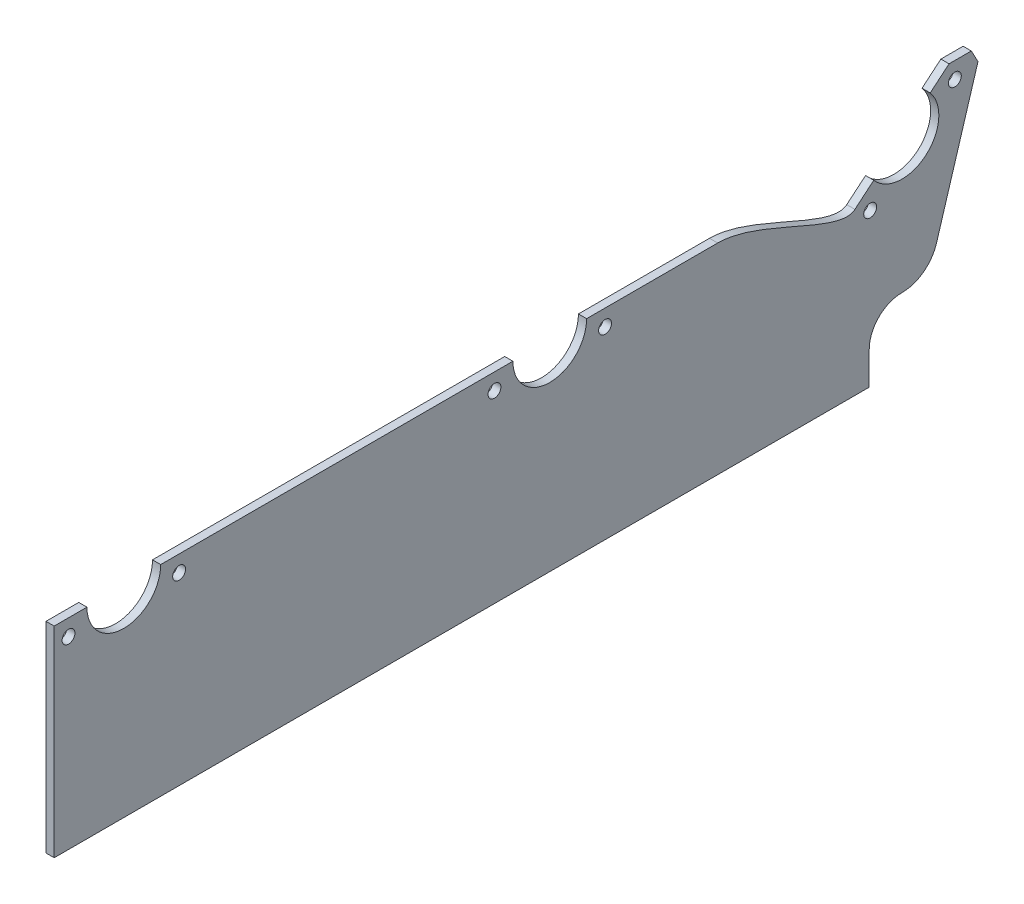
SolidWorks part; units mm, degrees
material "6061 Alloy"
ref_plane "Front Plane" through (0, 0, 0) normal (0, 0, 1) x (1, 0, 0)
ref_plane "Top Plane" through (0, 0, 0) normal (0, 1, 0) x (1, 0, 0)
ref_plane "Right Plane" through (0, 0, 0) normal (1, 0, 0) x (0, 0, -1)
sketch "Sketch1" plane through (0, 0, 0) normal (1, 0, 0) x (0, 0, -1)
  line L0 (-12.7, -12.7) -> (-328.6125, -12.7)
  line L1 (-328.6125, -12.7) -> (-328.6125, 65.0875)
  line L2 (-328.6125, 65.0875) -> (-315.9125, 65.0875)
  line L3 (-287.3375, 65.0875) -> (-150.8125, 65.0875)
  line L5 (10.9449, 74.2713) -> (18.2432, 80.3953)
  line L7 (-328.6125, 12.7) -> (13.3654, 12.7) construction
  line L8 (-12.7, -12.7) -> (-12.7, 0)
  line L9 (0, 12.4079) -> (0, 12.7) construction
  line L10 (13.3654, 22.6047) -> (30.9432, 80.3953)
  line L12 (-10.9449, 55.9037) -> (10.9449, 74.2713) construction
  line L13 (18.2432, 80.3953) -> (30.9432, 80.3953)
  line L14 (-122.2375, 65.0875) -> (-71.4375, 65.0875)
  line L15 (-10.9449, 55.9037) -> (-18.2432, 49.7797)
  line L18 (0, 65.0875) -> (-136.525, 65.0875) construction
  arc A3 (0, 12.7) -> (13.3654, 22.6047) centre (0, 26.67) ccw
  arc A4 (0, 12.7) -> (-12.7, 0) centre (0, 0) ccw
  circle A5 centre (0, 0) radius 12.4079 construction
  arc A6 (-315.9125, 65.0875) -> (-287.3375, 65.0875) centre (-301.625, 65.0875) ccw
  arc A7 (-150.8125, 65.0875) -> (-122.2375, 65.0875) centre (-136.525, 65.0875) ccw
  arc A8 (-10.9449, 55.9037) -> (10.9449, 74.2713) centre (0, 65.0875) ccw
  spline S0 degree 3 poles (-18.2432, 49.7797) (-24.729, 44.3374) (-54.5042, 65.0875) (-71.4375, 65.0875) knots 0 0 0 0 1 1 1 1
  point P4 (-170.6562, -12.7)
  dimension "D1" = 25.4
  dimension "D3" = 12.7
  dimension "D5" = 28.575
  dimension "D6" = 38.1
  dimension "D7" = 13.97
  dimension "D8" = 12.7
  dimension "D10" = 24.8158
  dimension "D13" = 9.5273
  dimension "D14" = 140
  dimension "D15" = 50.8
  dimension "D16" = 50.8
  dimension "D17" = 25.4
  dimension "D2" = 0
  dimension "D4" = 12.7
  dimension "D9" = 12.7
  dimension "D11" = 301.625
  dimension "D12" = 301.625
extrude "Boss-Extrude1" add sketch "Sketch1" along normal blind 3.175
hole_wizard "#10 Clearance Hole1" positions "Sketch2" profile "Sketch3" hole size "#10" standard "ANSI Inch" end condition through all
sketch "Sketch2" plane through (3.175, 0, 0) normal (1, 0, 0) x (0, 0, -1)
  line L0 (-323.0562, 58.7375) -> (-280.1937, 58.7375) construction
  line L2 (-157.9562, 58.7375) -> (-115.0937, 58.7375) construction
  line L4 (-12.3356, 46.4474) -> (20.499, 73.9989) construction
  line L6 (-315.9125, 65.0875) -> (-328.6125, 65.0875) construction
  line L7 (-301.625, 58.7375) -> (-301.625, 65.0875) construction
  line L9 (-136.525, 65.0875) -> (-136.525, 58.7375) construction
  line L11 (0, 65.0875) -> (4.0817, 60.2231) construction
  line L14 (18.2432, 80.3953) -> (10.9449, 74.2713) construction
  line L15 (18.2432, 80.3953) -> (10.9449, 74.2713) construction
  point P0 (-323.0562, 58.7375)
  point P2 (-280.1938, 58.7375)
  point P4 (-157.9562, 58.7375)
  point P6 (-115.0937, 58.7375)
  point P8 (-12.3356, 46.4474)
  point P10 (20.499, 73.9989)
  dimension "D1" = 42.8625
  dimension "D2" = 6.35
  dimension "D3" = 6.35
sketch "Sketch3" plane through (3.175, 58.7375, 323.0562) normal (0, 1, 0) x (0, 0, -1)
  line L0 (0, 0) -> (0, 3.175)
  line L1 (0, 3.175) -> (2.4892, 3.175)
  line L2 (2.4892, 3.175) -> (2.4892, 0)
  line L5 (2.4892, 0) -> (0, 0)
  line L11 (0, -6.35) -> (0, 107.95) construction
  dimension "Thru Hole Dia." = 4.9784
  dimension "Thru Hole Depth" = 3.175
chamfer "Chamfer1" distance 5.08 angle 45 1 edges at (1.5875, 80.3953, -30.9432) first distance on face at (1.5875, 51.5, -22.1543)
